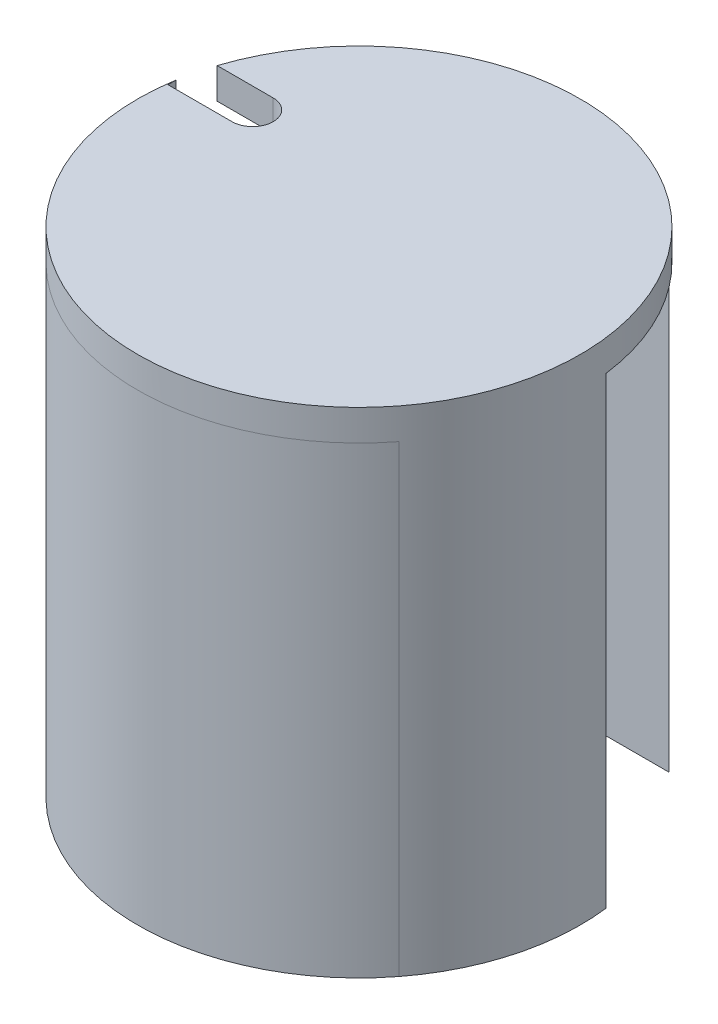
SolidWorks part; units mm, degrees
ref_plane "前基準面" through (0, 0, 0) normal (0, 0, 1) x (1, 0, 0)
ref_plane "上基準面" through (0, 0, 0) normal (0, 1, 0) x (1, 0, 0)
ref_plane "右基準面" through (0, 0, 0) normal (1, 0, 0) x (0, 0, -1)
sketch "草圖1" plane through (0, 0, 0) normal (0, 1, 0) x (1, 0, 0)
  line L1 (9.8985, 23.667) -> (9.8985, -19.333) construction
  line L3 (0.3985, 4.3356) -> (19.3985, 4.3356)
  line L4 (0.3985, -14.6644) -> (19.3985, -14.6644)
  line L5 (0.3985, 4.3356) -> (-11.4919, 4.3356)
  line L6 (-11.4919, 4.3356) -> (31.2888, 4.3356)
  line L7 (-3.0433, 19.3356) -> (22.8403, 19.3356)
  line L8 (-11.4353, 4.8356) -> (31.2322, 4.8356)
  circle A0 centre (9.8985, 2.167) radius 21.5
  circle A1 centre (19.3985, -5.1644) radius 9.5
  circle A3 centre (0.3985, -5.1644) radius 9.5
  dimension "D1" = 43
  dimension "D2" = 19
  dimension "D4" = 19
  dimension "D3" = 15
  dimension "D5" = 0.5
extrude "填料-伸長7" add sketch "草圖1" along normal blind 45 contours A0 L1 L7 | L1 A0 L7 | A1 A0 L6 | L8 L1 L6 A0 | L1 L8 A0 L5 L3 | A3 L5 A0 | L1 L4 A3 A0 | L4 L1 A0 A1 region at (14.8242, 0, -21.0841) region at (4.9728, 0, -21.0841) region at (20.58, 0, -4.5855) region at (-0.783, 0, -4.5855) region at (28.4806, 0, -0.611) region at (-8.6836, 0, -0.611) region at (4.389, 0, 16.4222) region at (15.408, 0, 16.4222)
sketch "草圖2" plane through (0, 45, 0) normal (0, 1, 0) x (1, 0, 0)
  circle A0 centre (9.8985, 2.167) radius 21.5
extrude "填料-伸長12" add sketch "草圖2" along normal blind 3 separate body
sketch "草圖3" plane through (0, 0, -4.8356) normal (0, 0, -1) x (-1, 0, 0)
  line L0 (-9.8985, 45) -> (-9.8985, 0) construction
  line L1 (3.0433, 45) -> (-22.8403, 45) construction
  line L2 (-22.8403, 0) -> (3.0433, 0) construction
  line L3 (11.4353, 45) -> (-31.2322, 45) construction
  line L4 (-24.8985, 42) -> (0.1015, 42)
  line L5 (-24.8985, 42) -> (-24.8985, 0)
  line L6 (-24.8985, 0) -> (0.1015, 0)
  line L7 (0.1015, 42) -> (0.1015, 0)
  line L8 (-26.8985, 45) -> (2.1015, 45)
  line L9 (-26.8985, 45) -> (-26.8985, 0)
  line L10 (-26.8985, 0) -> (2.1015, 0)
  line L11 (2.1015, 45) -> (2.1015, 0)
  line L12 (11.4353, 0) -> (-31.2322, 0) construction
  line M8 (-31.2322, 0) -> (11.4353, 0)
  line M10 (11.4353, 45) -> (-31.2322, 45)
  dimension "D1" = 25
  dimension "D2" = 15
  dimension "D3" = 42
  dimension "D4" = 29
  dimension "D5" = 17
extrude "填料-伸長13" add sketch "草圖3" along normal blind 3 contours L0 L8 L9 L5 L4 M8 | L0 L4 L7 L11 M10 M8 region at (3.8985, 44.5343, -4.8356) region at (10.3795, 43.5, -4.8356)
sketch "草圖6" plane through (0, 45, 0) normal (0, -1, 0) x (1, 0, 0)
  line L0 (-2.1015, -7.8356) -> (-2.1015, -4.8356) construction
  line L1 (-11.4353, -4.8356) -> (-2.1015, -4.8356) construction
  line L2 (-5.1015, -4.8356) -> (-11.3244, -4.8356)
  line L3 (-11.3244, -4.8356) -> (-11.3244, -8.8356)
  line L4 (-11.3244, -8.8356) -> (-5.1015, -8.8356)
  circle A0 centre (-5.1015, -6.8356) radius 2
  line M6 (-2.1015, -4.8356) -> (-11.4353, -4.8356)
  arc M7 (-11.4353, -4.8356) -> (31.2322, -4.8356) centre (9.8985, -2.167) ccw
  dimension "D1" = 4
  dimension "D2" = 3
  dimension "D3" = 2
extrude "除料-伸長1" cut sketch "草圖6" against normal blind 10 contours A0 L3 L4 M6 M7 | A0 M7 region at (-8.8422, 45, -6.772) region at (-5.1015, 45, -6.8356)
